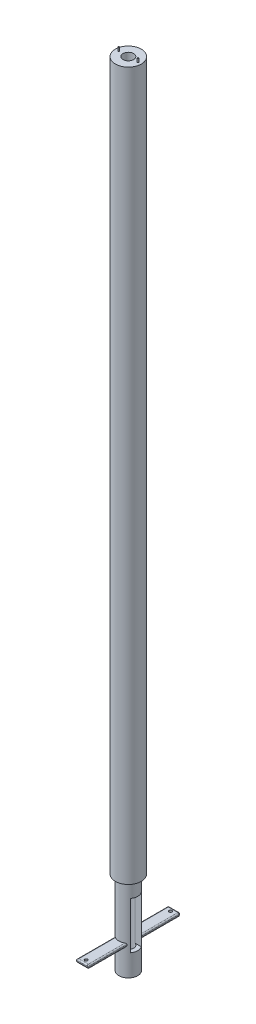
SolidWorks part; units mm, degrees
ref_plane "Front Plane" through (0, 0, 0) normal (0, 0, 1) x (1, 0, 0)
ref_plane "Top Plane" through (0, 0, 0) normal (0, 1, 0) x (1, 0, 0)
ref_plane "Right Plane" through (0, 0, 0) normal (1, 0, 0) x (0, 0, -1)
sketch "Sketch31" plane through (0, 0, 0) normal (0, 0, 1) x (1, 0, 0)
  line L0 (0, 0) -> (0, 35.4702)
sweep "Sweep3" add path "Sketch31" circular profile diameter 8 parameters "D3"=8
sketch "Sketch38" plane through (0, 0, 0) normal (0, 0, 1) x (1, 0, 0)
  line L1 (4, 35.4702) -> (-4, 35.4702) construction
  line L2 (0, 35.4702) -> (0, 336.2875)
sweep "Sweep4" add path "Sketch38" circular profile diameter 11 parameters "D3"=11
sketch "Sketch45" plane through (0, 0, 0) normal (0, 1, 0) x (1, 0, 0)
  circle A0 centre (0, 0) radius 2.25
extrude "Cut-Extrude2" cut sketch "Sketch45" along normal through all
sketch3d "3DSketch1"
  line L1 (0, 336.2875, 0) -> (0, 0, 0) construction
  line L2 (0, 336.2875, 0) -> (2.25, 336.2875, 0)
  line L18 (-5.5, 336.2875, 0) -> (-5.5, 336.2875, -5.5)
  line L19 (-5.5, 336.2875, -5.5) -> (0, 336.2875, -5.5)
  line L20 (0, 336.2875, -5.5) -> (5.5, 336.2875, -5.5)
  line L21 (5.5, 336.2875, -5.5) -> (5.5, 336.2875, 0)
  line L22 (0, 336.2875, 5.5) -> (5.5, 336.2875, 5.5)
  line L23 (5.5, 336.2875, 5.5) -> (5.5, 336.2875, 0)
  line L24 (0, 336.2875, 5.5) -> (-5.5, 336.2875, 5.5)
  line L25 (-5.5, 336.2875, 5.5) -> (-5.5, 336.2875, 0)
  circle A0 centre (0, 336.2875, 0) radius 2.25
  circle A1 centre (0, 336.2875, 0) radius 5.5 construction
  point P3 (0, 338.5375, 0)
  point P6 (0, 341.7875, 0)
  dimension "D1" = 5.5
  dimension "D3" = 5.5
  dimension "D2" = 5.5
  dimension "D4" = 5.5
  dimension "D5" = 5.5
  dimension "D6" = 5.5
  dimension "D7" = 5.5
  dimension "D8" = 5.5
sketch3d "3DSketch4"
  line L0 (4.125, 336.2875, 0) -> (4.125, 337.7875, 0)
  line L1 (-4.125, 336.2875, 0) -> (-4.125, 337.7875, 0)
  point P5 (-4.125, 336.2875, 0)
  point P6 (4.125, 336.2875, 0)
  dimension "D1" = 1.5
  dimension "D2" = 1.5
sweep "Sweep5" add path "3DSketch4" circular profile diameter 0.5 parameters "D3"=0.5
sketch3d "3DSketch5"
  line L0 (-4.125, 336.2875, 0) -> (-4.125, 337.7875, 0)
  line L1 (-5.5, 336.2875, 0) -> (-2.75, 336.2875, 0)
  line L2 (-4.125, 336.2875, 0) -> (-2.75, 336.2875, 0)
  dimension "D1" = 1.5
  dimension "D2" = 4.125
sweep "Sweep6" add path "3DSketch5" circular profile diameter 0.5 parameters "D3"=0.5
sketch "Sketch72" plane through (0, 0, 0) normal (1, 0, 0) x (0, 0, -1)
  line L0 (-2.318, 9.2361) -> (2.182, 9.2361)
  line L2 (-2.318, 9.2361) -> (-2.318, 29.2361)
  line L3 (-2.318, 29.2361) -> (2.182, 29.2361)
  line L4 (2.182, 29.2361) -> (2.182, 9.2361)
  dimension "D1" = 20
  dimension "D2" = 4.5
extrude "Cut-Extrude6" cut sketch "Sketch72" along normal blind 20
sketch "Sketch73" plane through (0, 0, 0) normal (0, 0, 1) x (1, 0, 0)
  line L0 (3.875, 337.7212) -> (4.3306, 337.589)
  line L1 (3.875, 337.7875) -> (3.875, 336.2875) construction
sketch "Sketch74" plane through (0, 0, 0) normal (0, 0, 1) x (1, 0, 0)
  point P5 (0, 12.0702)
sketch "Sketch76" plane through (0, 0, 0) normal (1, 0, 0) x (0, 0, -1)
  line L0 (3, 11.3702) -> (3, 12.7702)
  line L2 (-3, 12.0702) -> (-3, 12.7702)
  line L3 (3, 12.7702) -> (19.5, 12.7702)
  line L4 (-4, 35.4702) -> (4, 35.4702) construction
  line L5 (-3, 12.0702) -> (-3, 11.3702)
  line L6 (19.5, 11.3702) -> (19.5, 12.7702)
  line L7 (-19.5, 12.3702) -> (-19.5, 11.3702)
  line L8 (-19.5, 11.3702) -> (-3, 11.3702)
  line L9 (-19.5, 12.3702) -> (-19.5, 12.7702)
  line L10 (-19.5, 12.7702) -> (-3, 12.7702)
  line L12 (19.5, 11.3702) -> (3, 11.3702)
  line L14 (-3, 12.0702) -> (-3, 35.4702)
  dimension "D1" = 23.4
  dimension "D5" = 0.7
  dimension "D6" = 1.4
  dimension "D7" = 1.4
extrude "Boss-Extrude1" add sketch "Sketch76" along normal blind 2.5 and the other way blind 2.5 contours L10 L2 L5 L8 L7 L9
extrude "Boss-Extrude3" add sketch "Sketch76<4>" along normal blind 2.5 and the other way blind 2.5 contours L12 L6 L3 L0 region at (0, 12.0702, -11.25)
sketch "Sketch76<4>" plane through (0, 0, 0) normal (1, 0, 0) x (0, 0, -1) same geometry as "Sketch76"
sketch "Sketch77" plane through (0, 0, 0) normal (0, 1, 0) x (1, 0, 0)
  line L0 (-6.05, 0) -> (6.05, 0) construction
  circle A0 centre (0, 17.9) radius 0.6122
  circle A1 centre (0, -17.9) radius 0.6122
  point P7 (0, 0)
extrude "Cut-Extrude7" cut sketch "Sketch77" along normal blind 20
fillet "Fillet1" radius 0.5 14 edges at (-2.5, 12.7702, 11.3112) (-2.5, 11.3702, 11.3112) (2.5, 12.0702, 19.5) (0, 11.3702, 19.5) (2.5, 11.3702, 11.3112) (2.5, 12.7702, 11.3112) (0, 12.7702, 19.5) (-2.5, 11.3702, -11.3112) (-2.5, 12.7702, -11.3112) (0, 12.7702, -19.5) (0, 11.3702, -19.5) (2.5, 12.0702, -19.5) (2.5, 11.3702, -11.3112) (2.5, 12.7702, -11.3112)
